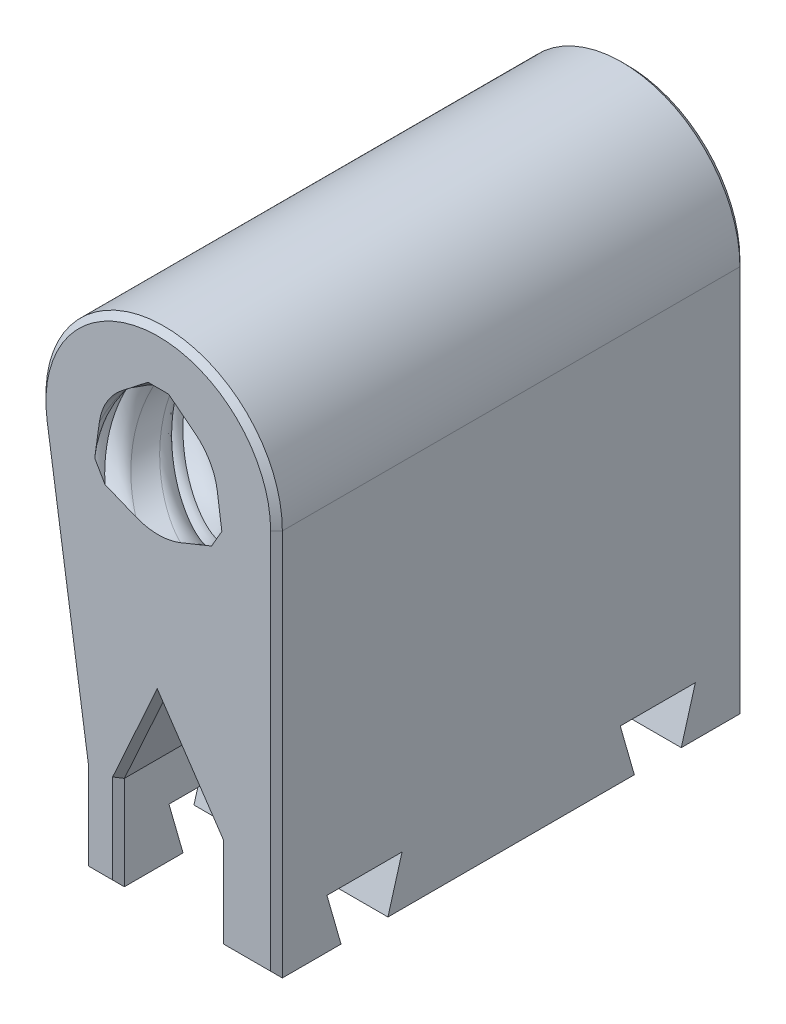
SolidWorks part; units mm, degrees
material "ABS"
ref_plane "Front Plane" through (0, 0, 0) normal (0, 0, 1) x (1, 0, 0)
ref_plane "Top Plane" through (0, 0, 0) normal (0, 1, 0) x (1, 0, 0)
ref_plane "Right Plane" through (0, 0, 0) normal (1, 0, 0) x (0, 0, -1)
sketch "Sketch1" plane through (0, 0, 0) normal (0, 0, 1) x (1, 0, 0)
  line L8 (0.5323, 28) -> (0.5323, -22)
  line L9 (-32.5377, -38) -> (-26.3977, -38)
  line L10 (-19.6177, 28) -> (-19.6177, -20.8617) construction
  line L11 (-32.5377, -38) -> (-32.5377, -22)
  line L12 (-32.5377, -22) -> (-26.3977, -22)
  line L13 (-26.3977, -38) -> (-26.3977, -22)
  line L14 (-9.4677, -38) -> (0.5323, -38)
  line L15 (-9.4677, -38) -> (-9.4677, -22)
  line L16 (-9.4677, -22) -> (0.5323, -22)
  line L17 (0.5323, -38) -> (0.5323, -22)
  line L18 (-9.4677, -22) -> (-19.6177, -7)
  line L19 (-19.6177, -7) -> (-26.3977, -22)
  line L20 (-32.5377, -22) -> (-39.5475, 25.0294)
  circle A0 centre (-19.6177, 28) radius 10.15
  circle A1 centre (-19.6177, 28) radius 20.15
  point P12 (0, 0)
  point P17 (-19.6177, -0.8786)
  point P18 (-19.6177, -6.4909)
  dimension "D7" = 10
  dimension "D8" = 20.3
  dimension "D1" = 16.93
  dimension "D2" = 10
  dimension "D3" = 16
  dimension "D4" = 6.14
  dimension "D5" = 50
  dimension "D6" = 15
extrude "Boss-Extrude1" add sketch "Sketch1" along normal blind 80 contours A1 L16 L12 | A1 L16 | A1 L16 A0 | A1 L12 L16 | A1 L16 | L16 A1 | A1 | A0 | L11 L9 L13 L12 region at (-18.1704, 8.4735, 0) region at (-16.8552, -2.9576, 0) region at (-4.4677, -30, 0)
sketch "Sketch2" plane through (0.5323, 0, 0) normal (1, 0, 0) x (0, 0, -1)
  line L0 (-61, -38) -> (-58.6, -29.6)
  line L1 (-80, -38) -> (0, -38) construction
  line L2 (-58.6, -29.6) -> (-71.4, -29.6)
  line L3 (-71.4, -29.6) -> (-69, -38)
  line L4 (-69, -38) -> (-61, -38)
  line L5 (-15, -29.6) -> (-15, -38)
  line L6 (-11, -38) -> (-19, -38)
  line L7 (-40, -38) -> (-40, 28) construction
  line L8 (-80, 28) -> (0, 28) construction
  line L9 (-65, -29.6) -> (-65, -38)
  line L10 (-8.6, -29.6) -> (-11, -38)
  line L11 (-21.4, -29.6) -> (-8.6, -29.6)
  line L12 (-19, -38) -> (-21.4, -29.6)
  line M10 (-80, -38) -> (0, -38)
  dimension "D1" = 25
  dimension "D2" = 12.8
  dimension "D3" = 4
  dimension "D4" = 8.4
  dimension "D5" = 4
extrude "Cut-Extrude1" cut sketch "Sketch2" against normal through all contours L9 L2 L3 M10 | L2 L9 L4 L0 | L12 L5 L11 M10 | L11 L5 L10 M10 region at (0.5323, -33.4769, 62.3538) region at (0.5323, -33.4769, 17.6462) region at (0.5323, -33.4769, 67.6462) region at (0.5323, -33.4769, 12.3538)
sketch "Sketch3" plane through (0, 0, 0) normal (0, 0, -1) x (-1, 0, 0)
  line L0 (13.3834, 36.0098) -> (17.8677, 39.5)
  line L1 (17.8677, 39.5) -> (21.3677, 39.5)
  line L2 (21.3677, 39.5) -> (25.8519, 36.0098)
  circle A0 centre (19.6177, 28) radius 10.15 construction
  arc A2 (13.3834, 36.0098) -> (25.8519, 36.0098) centre (19.6177, 28) cw
  dimension "D1" = 11.5
  dimension "D2" = 1.75
  dimension "D3" = 3.5
sketch "Sketch5" plane through (0, 0, 0) normal (0, 0, -1) x (-1, 0, 0)
  circle A0 centre (19.6177, 28) radius 8
curve "Helix/Spiral1" pitch 40 height 90 radius 8 centre (-19.6177, 28, 0) axis (0, 0, 1) start towards (0, 1, 0)
sweep "Cut-Sweep3" cut profiles "Sketch3" path "Helix/Spiral1" align with end faces yes
pattern_circular "CirPattern1" count 3 over 360 about axis through (-19.6177, 28, 80) along (0, 0, -1) of "Cut-Sweep3" reverse direction yes
chamfer "Chamfer1" distance 1 angle 45 10 edges at (-29.4677, -38, 80) (-32.5377, -30, 80) (-26.3977, -30, 80) (-23.0077, -14.5, 80) (-14.5427, -14.5, 80) (-9.4677, -30, 80) (-4.4677, -38, 80) (0.5323, -5, 80) (-21.107, 48.0949, 80) (-36.0426, 1.5147, 80)
chamfer "Chamfer2" distance 1 angle 45 10 edges at (0.5323, -5, 0) (-4.4677, -38, 0) (-9.4677, -30, 0) (-14.5427, -14.5, 0) (-23.0077, -14.5, 0) (-26.3977, -30, 0) (-29.4677, -38, 0) (-32.5377, -30, 0) (-36.0426, 1.5147, 0) (-21.107, 48.0949, 0)
equation "\"D1@Boss-Extrude1\"= 68.00- 6.63"
equation "\"D5@Sketch2\"=\"D3@Sketch2\""
equation "\"D2@Sketch3\"=\"D3@Sketch3\"/2"
